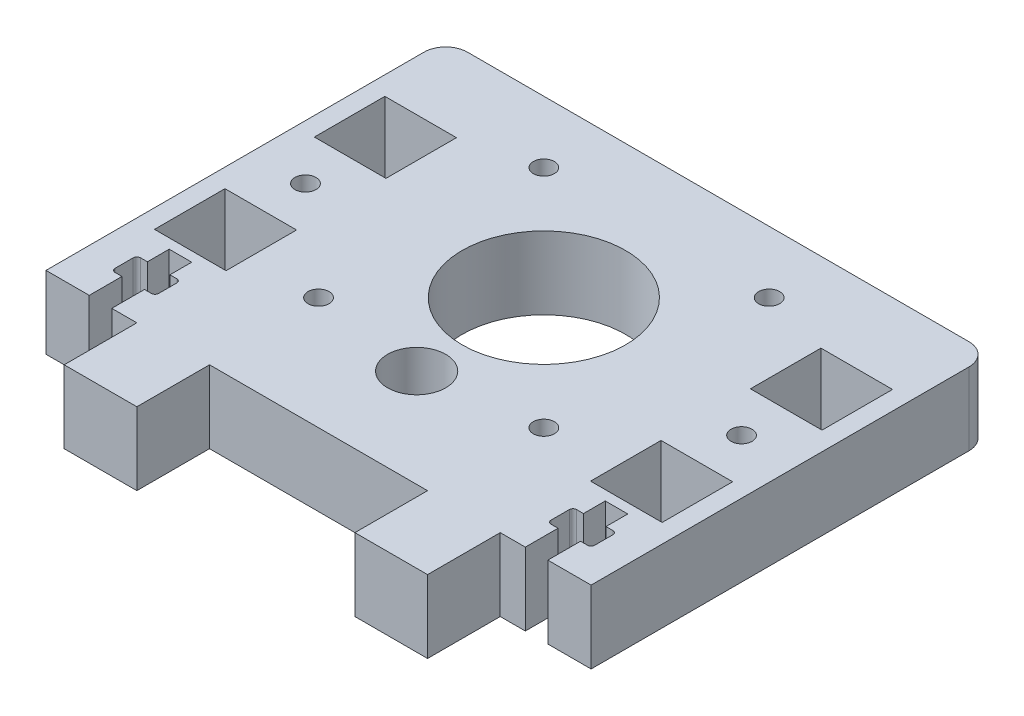
SolidWorks part; units mm, degrees
ref_plane "Front Plane" through (0, 0, 0) normal (0, 0, 1) x (1, 0, 0)
ref_plane "Top Plane" through (0, 0, 0) normal (0, 1, 0) x (1, 0, 0)
ref_plane "Right Plane" through (0, 0, 0) normal (1, 0, 0) x (0, 0, -1)
sketch "Sketch1" plane through (0, 0, 0) normal (0, 1, 0) x (1, 0, 0)
  line L0 (0, 29) -> (0, -8.5) construction
  line L1 (-34.5, 29) -> (0, 29)
  line L2 (-37.5, 26) -> (-37.5, -26)
  line L3 (-37.5, -26) -> (-25, -26)
  line L4 (0, 29) -> (0, 16.25)
  line L5 (0, -6.25) -> (0, -8.5)
  line L6 (0, -16.5) -> (0, -26) construction
  line L7 (-11.25, 5) -> (0, 5) construction
  line L8 (0, -16.5) -> (0, -26)
  line L9 (-30, 18.05) -> (-30, 8.35) construction
  line L10 (-37.5, 2.2) -> (0, 2.2) construction
  line L11 (-34.925, 18.05) -> (-25.075, 18.05)
  line L12 (-34.925, 18.05) -> (-34.925, 8.35)
  line L13 (-34.925, 8.35) -> (-25.075, 8.35)
  line L14 (-25.075, 18.05) -> (-25.075, 8.35)
  line L15 (-34.925, 18.05) -> (-25.075, 8.35) construction
  line L16 (-34.925, 8.35) -> (-25.075, 18.05) construction
  line L17 (-34.925, -3.95) -> (-25.075, -13.65) construction
  line L18 (-34.925, -13.65) -> (-25.075, -3.95) construction
  line L19 (-25.075, -13.65) -> (-25.075, -3.95)
  line L20 (-34.925, -3.95) -> (-25.075, -3.95)
  line L21 (-34.925, -13.65) -> (-34.925, -3.95)
  line L22 (-34.925, -13.65) -> (-25.075, -13.65)
  line L23 (-30, -3.95) -> (-30, -13.65) construction
  line L24 (-30, -8.8) -> (-30, 13.2) construction
  line L25 (0, 5) -> (-15.5, 20.5) construction
  line L35 (-15, -26) -> (0, -26)
  line L43 (-20, -36) -> (-20, -24.65) construction
  line L44 (-15, -26) -> (-15, -36)
  line L45 (-15, -36) -> (-25, -36)
  line L46 (-25, -36) -> (-25, -26)
  arc A1 (-34.5, 29) -> (-37.5, 26) centre (-34.5, 26) ccw
  arc A2 (0, 16.25) -> (0, -6.25) centre (0, 5) ccw
  circle A4 centre (-15.5, 20.5) radius 1.45
  circle A6 centre (-15.5, -10.5) radius 1.45
  circle A7 centre (-30, 2.2) radius 1.45
  arc A10 (0, -8.5) -> (0, -16.5) centre (0, -12.5) ccw
  point P0 (0, 0)
  point P28 (-30, 13.2)
  point P39 (-30, -8.8)
  dimension "D7" = 22.5
  dimension "D17" = 8
  dimension "D14" = 2.9
  dimension "D6" = 3
  dimension "D19" = 2.9
  dimension "D1" = 55
  dimension "D9" = 9.85
  dimension "D10" = 9.7
  dimension "D22" = 10
  dimension "D23" = 10
  dimension "D16" = 17.5
  dimension "D11" = 22
  dimension "D13" = 2.2
  dimension "D3" = 37.5
  dimension "D4" = 31
  dimension "D5" = 15.5
  dimension "D15" = 26
  dimension "D18" = 37.5
  dimension "D20" = 20
  dimension "D8" = 13.5
  dimension "D12" = 30
extrude "MainLayout" add sketch "Sketch1" along normal blind 10
sketch "Sketch2" plane through (0, 10, 0) normal (0, 1, 0) x (1, 0, 0)
  line L0 (-30, -26) -> (-30, -15) construction
  line L1 (-28.45, -21.5) -> (-28.45, -26)
  line L2 (-37.5, -26) -> (-25, -26) construction
  line L3 (-28.45, -15) -> (-31.55, -15)
  line L4 (-31.55, -15) -> (-31.55, -18)
  line L5 (-31.55, -18) -> (-32.5, -18)
  line L6 (-33, -18.5) -> (-33, -21)
  line L7 (-32.5, -21.5) -> (-31.55, -21.5)
  line L8 (-31.55, -21.5) -> (-31.55, -26)
  line L9 (-31.55, -26) -> (-28.45, -26)
  line L10 (-27.5, -21.5) -> (-28.45, -21.5)
  line L11 (-27, -18.5) -> (-27, -21)
  line L12 (-28.45, -18) -> (-27.5, -18)
  line L13 (-28.45, -15) -> (-28.45, -18)
  line L14 (0, -26) -> (0, -16.5) construction
  line L30 (-30, -26) -> (-30, -15) construction
  arc A0 (-27, -18.5) -> (-27.5, -18) centre (-27.5, -18.5) ccw
  arc A1 (-32.5, -18) -> (-33, -18.5) centre (-32.5, -18.5) ccw
  arc A2 (-27.5, -21.5) -> (-27, -21) centre (-27.5, -21) ccw
  arc A3 (-33, -21) -> (-32.5, -21.5) centre (-32.5, -21) ccw
  point P17 (0, -21.25)
  point P38 (-27, -18)
  point P41 (-33, -18)
  point P44 (-27, -21.5)
  point P47 (-33, -21.5)
  dimension "D8" = 0.5
  dimension "D1" = 1.55
  dimension "D2" = 0
  dimension "D3" = 3.5
  dimension "D5" = 11
  dimension "D6" = 3
  dimension "D4" = 8
  dimension "D7" = 30
extrude "TSlot" cut sketch "Sketch2" against normal through all
mirror "Mirror1" about plane through (0, 0, 0) normal (1, 0, 0) of "TSlot", "MainLayout"
equation "\"Y-ROD-SPACING\"=75"
equation "\"Y-BED-OFFSET\"=2"
equation "\"Y-BED-ROD-INSET\"=3.5"
equation "\"T-SLOT-NUT-FILLET-RADIUS\"=0.5"
equation "\"T-SLOT-SCREW-SHAFT-RADIUS\"=1.55"
equation "\"T-SLOT-SCREW-SHAFT-CUTOUT-LENGTH\"=11"
equation "\"T-SLOT-NUT-DEPTH\"=3.5"
equation "\"T-SLOT-NUT-WIDTH\"=2.85"
equation "\"T-SLOT-NUT-END-DISTANCE\"=8"
equation "\"ACRYLIC-TAB-CUTOUT-SIZE\"=\"ACRYLIC-THICKNESS\"+\"ACRYLIC-TAB-TOLERANCE\"*2"
equation "\"ACRYLIC-TAB-WIDTH\"=\"ACRYLIC-THICKNESS\""
equation "\"ACRYLIC-M3-HOLE\"=2.9"
equation "\"SMOOTHROD-CAP-SCREW-DISTANCE\"=20"
equation "\"FRAME-WIDTH-INNER\"=370"
equation "\"NEMA17-HOLE-SPACING\"=31"
equation "\"NEMA17-CENTRAL-CUTOUT\"=22.5"
equation "\"D7@Sketch1\"=\"NEMA17-CENTRAL-CUTOUT\""
equation "\"D5@Sketch1\"=\"NEMA17-HOLE-SPACING\"/2"
equation "\"D4@Sketch1\"=\"NEMA17-HOLE-SPACING\""
equation "\"D19@Sketch1\"=\"ACRYLIC-M3-HOLE\""
equation "\"D14@Sketch1\"=\"ACRYLIC-M3-HOLE\""
equation "\"D9@Sketch1\"=\"ACRYLIC-THICKNESS\"-\"KERF\"*2"
equation "\"D10@Sketch1\"=\"ACRYLIC-TAB-WIDTH\"-\"KERF\"*4"
equation "\"D23@Sketch1\"=\"ACRYLIC-TAB-WIDTH\""
equation "\"D22@Sketch1\"=\"ACRYLIC-TAB-WIDTH\""
equation "\"D5@Sketch2\"=\"T-SLOT-SCREW-SHAFT-CUTOUT-LENGTH\""
equation "\"D4@Sketch2\"=\"T-SLOT-NUT-END-DISTANCE\""
equation "\"D3@Sketch2\"=\"T-SLOT-NUT-DEPTH\""
equation "\"D1@Sketch2\"=\"T-SLOT-SCREW-SHAFT-RADIUS\""
equation "\"D8@Sketch2\"=\"T-SLOT-NUT-FILLET-RADIUS\""
equation "\"Z-BRACKET-REACH\"=55"
equation "\"D1@Sketch1\"=\"Z-BRACKET-REACH\""
equation "\"Z-ROD-SPACING\"=17.5"
equation "\"ACRYLIC-THICKNESS\"=10"
equation "\"TOP-BRACKET-SPACING\"=40"
equation "\"SMOOTHROD-X-LENGTH\"=350"
equation "\"SMOOTHROD-Y-LENGTH\"=350"
equation "\"SMOOTHROD-Z-LENGTH\"=350"
equation "\"SMOOTHROD-TIGHTENING-HEADROOM\"=.25"
equation "\"LEADSCREW-Z-LENGTH\"=300"
equation "\"D16@Sketch1\"=\"Z-ROD-SPACING\""
equation "\"X-ROD-SPACING\"=45"
equation "\"ACRYLIC-THICKNESS2\"=4.5"
equation "\"SCREW-LENGTH-FRAME\"=\"ACRYLIC-THICKNESS\" + 10"
equation "\"SCREW-HEAD-RADIUS\"=6"
equation "\"PRINTED-X-SMOOTHROD-DIAMETER\"=8.8"
equation "\"PRINTED-X-SMOOTHROD-CUTOUT\"=10"
equation "\"PRINTED-X-BASE-HEIGHT\"=10"
equation "\"PRINTED-LM8UU-CUTOUT-SIZE\"=15.5"
equation "\"PRINTED-LM8UU-CUTOUT-LENGTH\"=24.5"
equation "\"PRINTED-X-IDLER-HEIGHT\"=16"
equation "\"PSU-MOUNTING-WIDTH\"=95"
equation "\"PSU-MOUNTING-HEIGHT\"=177"
equation "\"D1@MainLayout\"=\"ACRYLIC-THICKNESS\""
equation "\"Z-ROD-INSET\"=13.5"
equation "\"Y-BELT-TO-ROD-DISTANCE\"=20"
equation "\"SPOOL-HOLDER-ROD-SPACING\"=150"
equation "\"D8@Sketch1\"=\"Z-ROD-INSET\""
equation "\"Y-BED-SCREW-SPACING\"=209"
equation "\"Y-BED-SCREW-CUTOUT-SLOT-HEIGHT\"=2"
equation "\"ACRYLIC-TAB-TOLERANCE\"=-.05"
equation "\"SCREW-LENGTH-MOTOR\"=\"ACRYLIC-THICKNESS\" + 5"
equation "\"SCREW-LENGTH-EXTRUDER\"=28"
equation "\"ACRYLIC-X-CARRIAGE-WIDTH\"=55"
equation "\"ACRYLIC-X-CARRIAGE-HEIGHT\"=75"
equation "\"ACRYLIC-X-CARRIAGE-LM8UU-CUTOUT-WIDTH\"=24.25"
equation "\"ACRYLIC-X-CARRIAGE-SCREW-SPACING-X\"=15"
equation "\"ACRYLIC-X-CARRIAGE-SCREW-SPACING-Y\"=33"
equation "\"ACRYLIC-X-CARRIAGE-CENTER-TAB-SPACING\"=14"
equation "\"ACRYLIC-X-CARRIAGE-EXTRUDER-OFFSET\"=26"
equation "\"ACRYLIC-X-CARRIAGE-EXTRUDER-ANGLE\"=90"
equation "\"ACRYLIC-X-CARRIAGE-EXTRUDER-SHELF-DEPTH\"=\"ACRYLIC-X-CARRIAGE-EXTRUDER-OFFSET\" + 28"
equation "\"ACRYLIC-X-CARRIAGE-EXTRUDER-BRACE-SPACING\"=23"
equation "\"ACRYLIC-X-CARRIAGE-EXTRUDER-BRACE-TAB-OFFSET\"=20"
equation "\"ACRYLIC-X-CARRIAGE-EXTRUDER-BRACE-HEIGHT\"=35"
equation "\"ACRYLIC-X-CARRIAGE-EXTRUDER-BRACE-SCREW-SPACING\"=22"
equation "\"KERF\"=0.075"
equation "\"PRINTED-M3-HOLE\"=3.5"
equation "\"PRINTED-M3-NUT-AF\"=6.25"
equation "\"ACRYLIC-X-CARRIAGE-LM8UU-CUTOUT-HEIGHT\"=11.0"
equation "\"ACRYLIC-X-CARRIAGE-DUAL-WIDTH-MULTIPLIER\"=1.65"
equation "\"ACRYLIC-X-CARRIAGE-DUAL-HOTEND-SPACING\"=42"
equation "\"ACRYLIC-X-CARRIAGE-DUAL-WIDTH\"=75"
equation "\"ACRYLIC-X-CARRIAGE-DUAL-FAN-OFFSET\"=52"
equation "\"ACRYLIC-X-CARRIAGE-DUAL-FAN-HEIGHT\"=20"
equation "\"ACRYLIC-X-CARRIAGE-DUAL-HOTEND-SEPARATION\"=36"
equation "\"ACRYLIC-X-CARRIAGE-DUAL-MOUNT-PLATE-DEPTH\"=75"
equation "\"ACRYLIC-X-CARRIAGE-DUAL-MOUNT-BRACE-WIDTH\"=33"
equation "\"ACRYLIC-X-CARRIAGE-DUAL-MOUNT-SCREW-WIDTH\"=40"
equation "\"BLOWER-FAN-WIDTH\"=15"
